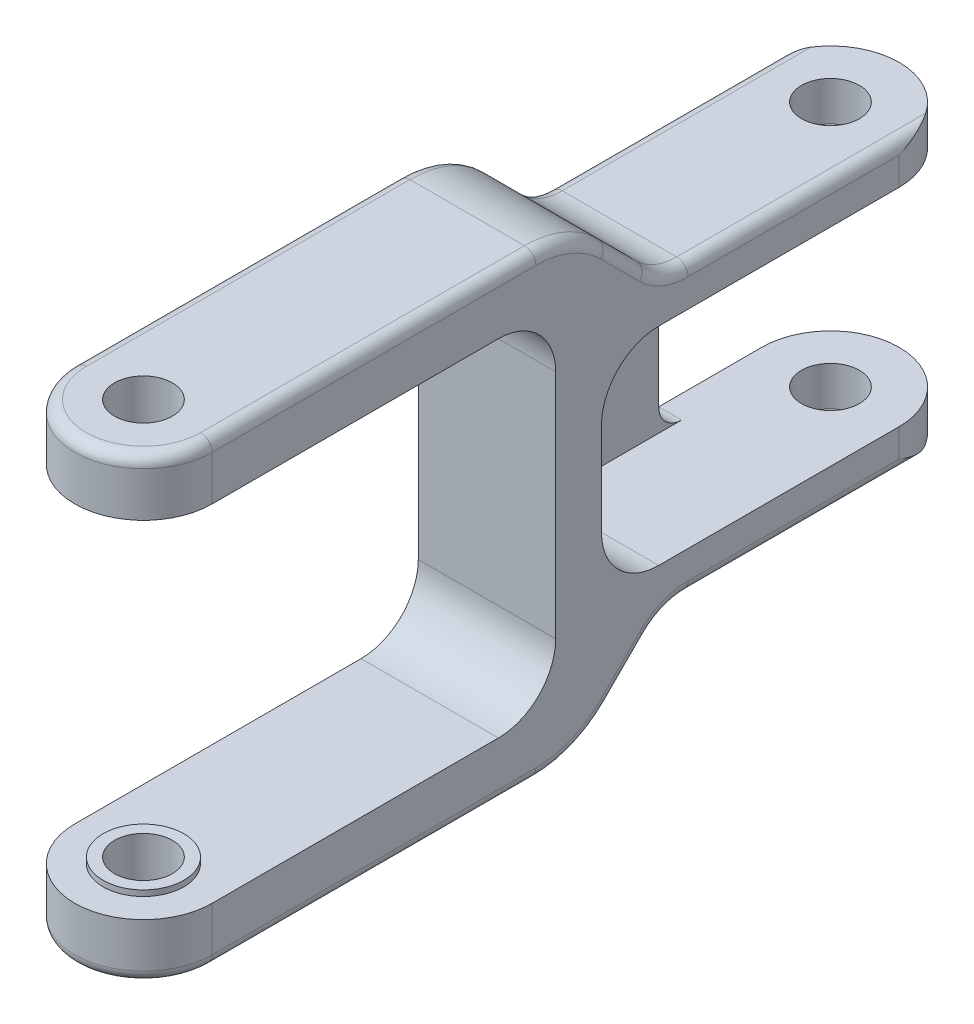
SolidWorks part; units mm, degrees
ref_plane "前视基准面" through (0, 0, 0) normal (0, 0, 1) x (1, 0, 0)
ref_plane "上视基准面" through (0, 0, 0) normal (0, 1, 0) x (1, 0, 0)
ref_plane "右视基准面" through (0, 0, 0) normal (1, 0, 0) x (0, 0, -1)
other "Configuration Table"
ref_plane "基准面1" through (0, -20, 0) normal (0, -1, 0) x (1, 0, 0)
sketch "草图1" plane through (0, -20, 0) normal (0, -1, 0) x (1, 0, 0)
  line L0 (-6, 0) -> (-6, -60)
  line L1 (6, -60) -> (6, 0)
  arc A0 (-6, -60) -> (6, -60) centre (0, -60) ccw
  arc A1 (6, 0) -> (-6, 0) centre (0, 0) ccw
  dimension "D1" = 6
  dimension "D2" = 60
extrude "凸台-拉伸1" add sketch "草图1" against normal blind 40
sketch "草图2" plane through (-6, 0, 0) normal (-1, 0, 0) x (0, 0, 1)
  line L0 (-66, -9.05) -> (-49, -9.05)
  line L1 (-49, -9.05) -> (-49, 9.05)
  line L2 (-49, 9.05) -> (-66, 9.05)
  line L3 (-66, 9.05) -> (-66, -9.05)
  line L4 (0, -20) -> (-60, -20) construction
  line L5 (-66, 20) -> (-66, -20) construction
  dimension "D1" = 49
  dimension "D3" = 10.95
  dimension "D4" = 29.05
extrude "切除-拉伸1" cut sketch "草图2" against normal through all
ref_plane "基准面2" through (0, 0, -49) normal (0, 0, -1) x (-1, 0, 0)
ref_plane "基准面3" through (0, 0, -34) normal (0, 0, 1) x (1, 0, 0)
sketch "草图4" plane through (0, 0, -34) normal (0, 0, 1) x (1, 0, 0)
  line L0 (-4, 9.05) -> (-4, -9.05)
  line L1 (-4, -9.05) -> (6, -9.05)
  line L2 (6, -9.05) -> (6, 9.05)
  line L3 (6, 9.05) -> (-4, 9.05)
  dimension "D1" = 10
  dimension "D2" = 18.1
extrude "切除-拉伸2" cut sketch "草图4" against normal up to surface up to plane "基准面2"
sketch "草图5" plane through (6, 0, 0) normal (1, 0, 0) x (0, 0, -1)
  line L0 (-6, -15.1) -> (30, -15.1)
  line L1 (30, -15.1) -> (30, 15.1)
  line L2 (30, 15.1) -> (-6, 15.1)
  line L3 (-6, 15.1) -> (-6, -15.1)
  line L4 (60, -9.05) -> (34, -9.05) construction
  line L5 (-6, 20) -> (-6, -20) construction
  dimension "D1" = 30
  dimension "D3" = 24.15
  dimension "D4" = 6.05
extrude "切除-拉伸3" cut sketch "草图5" against normal through all
sketch "草图6" plane through (6, 0, 0) normal (1, 0, 0) x (0, 0, -1)
  line L0 (39.5, 12.5) -> (60, 12.5)
  line L1 (66, 9.05) -> (66, 20) construction
  line L2 (60, 20) -> (32, 20)
  line L3 (32, 20) -> (39.5, 12.5)
  line L4 (60, -20) -> (0, -20) construction
  line L5 (60, 12.5) -> (66, 12.5)
  line L6 (66, -20) -> (66, 20) construction
  line L7 (66, 12.5) -> (66, 20)
  line L8 (66, 20) -> (60, 20)
  dimension "D1" = 32
  dimension "D2" = 39.5
  dimension "D3" = 60
  dimension "D4" = 32.5
  dimension "D5" = 40
extrude "切除-拉伸4" cut sketch "草图6" against normal through all
sketch "草图7" plane through (6, 0, 0) normal (1, 0, 0) x (0, 0, -1)
  line L0 (60, -12.5) -> (39.5, -12.5)
  line L1 (39.5, -12.5) -> (32, -20)
  line L2 (32, -20) -> (60, -20)
  line L4 (0, 20) -> (0, 15.1) construction
  line L5 (32, 20) -> (0, 20) construction
  line L6 (60, -12.5) -> (66, -12.5)
  line L7 (66, -20) -> (66, 12.5) construction
  line L8 (66, -12.5) -> (66, -20)
  line L9 (66, -20) -> (60, -20)
  dimension "D1" = 32
  dimension "D2" = 39.5
  dimension "D3" = 60
  dimension "D4" = 32.5
  dimension "D5" = 40
extrude "切除-拉伸5" cut sketch "草图7" against normal through all
sketch "草图8" plane through (0, 0, 0) normal (0, 0, 1) x (1, 0, 0)
  line L0 (3.525, -14.6) -> (0, -14.6)
  line L1 (0, -14.6) -> (0, -15.1)
  line L2 (0, -15.1) -> (3.525, -15.1)
  line L3 (3.525, -15.1) -> (3.525, -14.6)
  line L4 (0, -14.6) -> (0, -15.1) construction
  dimension "D1" = 3.525
  dimension "D2" = 0.5
revolve "旋转1" add sketch "草图8" angle 360 about L4
ref_plane "基准面4" through (0, 0, 0) normal (0, 0, -1) x (-1, 0, 0)
sketch "草图9" plane through (0, 0, 0) normal (0, 0, -1) x (-1, 0, 0)
  line L0 (-3.525, 14.6) -> (0, 14.6)
  line L1 (0, 14.6) -> (0, 15.1)
  line L2 (0, 15.1) -> (-3.525, 15.1)
  line L3 (-3.525, 15.1) -> (-3.525, 14.6)
  line L4 (0, 14.6) -> (0, 15.1) construction
  dimension "D1" = 3.525
  dimension "D2" = 0.5
revolve "旋转2" add sketch "草图9" angle 360 about L4
hole_wizard "孔1" positions "草图11" profile "草图10" legacy
sketch "草图11" plane through (0, 12.5, 0) normal (0, 1, 0) x (1, 0, 0)
  point P0 (0, 60)
sketch "草图10" plane through (0, 12.5, -60) normal (1, 0, 0) x (0, 0, 1)
  line L0 (0, 0) -> (0, 3.45)
  line L1 (0, 3.45) -> (2.525, 3.45)
  line L2 (2.525, 3.45) -> (2.525, 0)
  line L3 (2.525, 0) -> (0, 0)
  line L4 (0, 110) -> (0, -10) construction
  dimension "直径" = 5.05
  dimension "深度" = 3.45
hole_wizard "孔2" positions "草图13" profile "草图12" legacy
sketch "草图13" plane through (0, -9.05, 0) normal (0, 1, 0) x (1, 0, 0)
  point P0 (0, 60)
sketch "草图12" plane through (0, -9.05, -60) normal (1, 0, 0) x (0, 0, 1)
  line L0 (0, 0) -> (0, 3.45)
  line L1 (0, 3.45) -> (2.525, 3.45)
  line L2 (2.525, 3.45) -> (2.525, 0)
  line L3 (2.525, 0) -> (0, 0)
  line L4 (0, 110) -> (0, -10) construction
  dimension "直径" = 5.05
  dimension "深度" = 3.45
hole_wizard "孔3" positions "草图15" profile "草图14" legacy
sketch "草图15" plane through (0, -14.6, 0) normal (0, 1, 0) x (1, 0, 0)
  point P0 (0, 0)
sketch "草图14" plane through (0, -14.6, 0) normal (1, 0, 0) x (0, 0, 1)
  line L0 (0, 0) -> (0, 5.4)
  line L1 (0, 5.4) -> (2.525, 5.4)
  line L2 (2.525, 5.4) -> (2.525, 0)
  line L3 (2.525, 0) -> (0, 0)
  line L4 (0, 110) -> (0, -10) construction
  dimension "直径" = 5.05
  dimension "深度" = 5.4
hole_wizard "孔4" positions "草图17" profile "草图16" legacy
sketch "草图17" plane through (0, 20, 0) normal (0, 1, 0) x (1, 0, 0)
  point P0 (0, 0)
sketch "草图16" plane through (0, 20, 0) normal (1, 0, 0) x (0, 0, 1)
  line L0 (0, 0) -> (0, 5.4)
  line L1 (0, 5.4) -> (2.525, 5.4)
  line L2 (2.525, 5.4) -> (2.525, 0)
  line L3 (2.525, 0) -> (0, 0)
  line L4 (0, 110) -> (0, -10) construction
  dimension "直径" = 5.05
  dimension "深度" = 5.4
fillet "圆角1" radius 5 6 edges at (1, 9.05, -34) (0, 15.1, -30) (0, -15.1, -30) (1, -9.05, -34) (0, -12.5, -39.5) (0, 12.5, -39.5)
fillet "圆角2" radius 9 2 edges at (0, -20, -32) (0, 20, -32)
fillet "圆角3" radius 1 22 edges at (-6, 15.6642, -36.3358) (-6, 19.3149, -31.7162) (-6, 12.8806, -39.6577) (-6, 20, -14.136) (-6, 12.5, -50.7855) (0, 20, 6) (6, 20, -14.136) (6, 12.5, -50.7855) (6, 19.3149, -31.7162) (6, 12.8806, -39.6577) (6, 15.6642, -36.3358) (6, -12.8806, -39.6577) (6, -15.6642, -36.3358) (6, -12.5, -50.7855) (6, -19.3149, -31.7162) (6, -20, -14.136) (-6, -12.5, -50.7855) (0, -20, 6) (-6, -12.8806, -39.6577) (-6, -20, -14.136) (-6, -15.6642, -36.3358) (-6, -19.3149, -31.7162)
fillet "圆角4" radius 2 2 edges at (-5, 9.05, -49) (-5, -9.05, -49)
